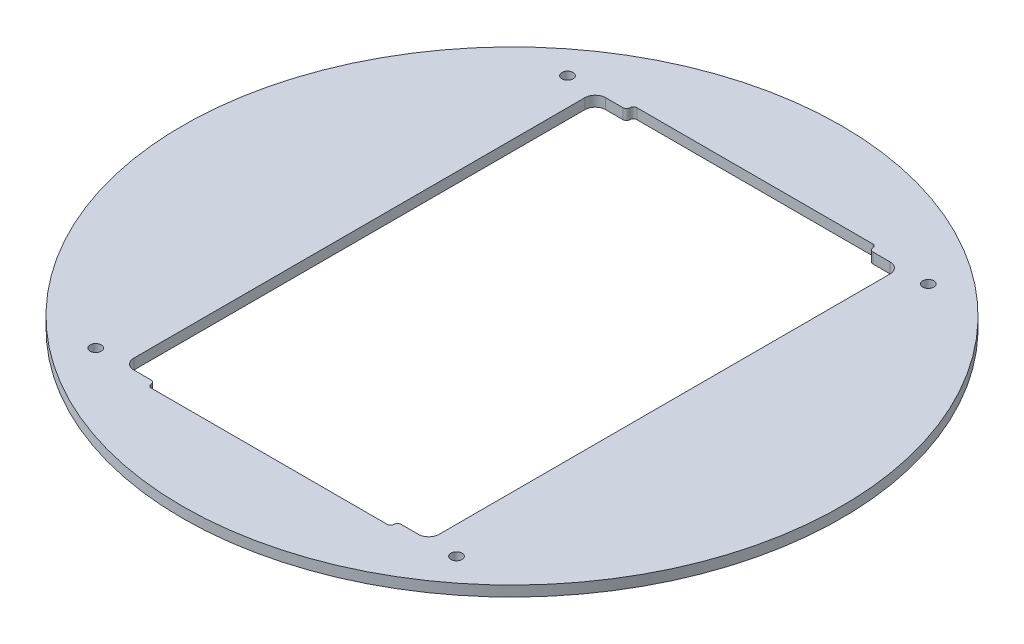
SolidWorks part; units mm, degrees
ref_plane "Ebene vorne" through (0, 0, 0) normal (0, 0, 1) x (1, 0, 0)
ref_plane "Ebene oben" through (0, 0, 0) normal (0, 1, 0) x (1, 0, 0)
ref_plane "Ebene rechts" through (0, 0, 0) normal (1, 0, 0) x (0, 0, -1)
sketch "Skizze1" plane through (0, 0, 0) normal (0, 1, 0) x (1, 0, 0)
  line L0 (-44, 65) -> (-44, -65)
  line L1 (-41, 68) -> (41, 68)
  line L5 (-41, -68) -> (41, -68)
  line L7 (44, 65) -> (44, -65)
  circle A0 centre (-52, 68) radius 1.6
  circle A1 centre (52, 68) radius 1.6
  circle A2 centre (-52, -68) radius 1.6
  circle A3 centre (52, -68) radius 1.6
  circle A8 centre (0, 0) radius 95
  arc A9 (-44, -65) -> (-41, -68) centre (-41, -65) ccw
  arc A10 (44, -65) -> (41, -68) centre (41, -65) cw
  arc A11 (44, 65) -> (41, 68) centre (41, 65) ccw
  arc A12 (-44, 65) -> (-41, 68) centre (-41, 65) cw
  point P0 (0, 0)
  point P12 (-44, -68)
  point P23 (44, 68)
  point P26 (-44, 68)
  dimension "D3" = 3
  dimension "D1" = 104
  dimension "D2" = 136
extrude "Aufsatz-Linear austragen1" add sketch "Skizze1" along normal blind 3
sketch "Skizze2" plane through (0, 0, 0) normal (0, 1, 0) x (1, 0, 0)
  line L0 (41, 68) -> (-41, 68) construction
  line L1 (-35, 70) -> (35, 70)
  line L2 (-35, 70) -> (-35, 66)
  line L3 (-35, 66) -> (35, 66)
  line L4 (35, 70) -> (35, 66)
  line L5 (-35, 70) -> (35, 66) construction
  line L6 (-35, 66) -> (35, 70) construction
  line L7 (0, 0) -> (-35, 0)
  line L8 (-35, -66) -> (35, -70) construction
  line L9 (-35, -70) -> (35, -66) construction
  line L10 (35, -70) -> (35, -66)
  line L11 (-35, -66) -> (35, -66)
  line L12 (-35, -70) -> (-35, -66)
  line L13 (-35, -70) -> (35, -70)
  point P0 (0, 68)
  point P14 (0, -68)
  dimension "D1" = 70
  dimension "D3" = 70
extrude "Schnitt-Linear austragen2" cut sketch "Skizze2" along normal blind 3 contours L12 L13 L10 L11 | L4 L1 L2 L3 region at (0, 0, -68) region at (0, 0, 68)
fillet "Verrundung1" radius 1 8 edges at (-35, 1.5, 68) (-35, 1.5, 70) (35, 1.5, 70) (35, 1.5, 68) (35, 1.5, -68) (35, 1.5, -70) (-35, 1.5, -70) (-35, 1.5, -68)
